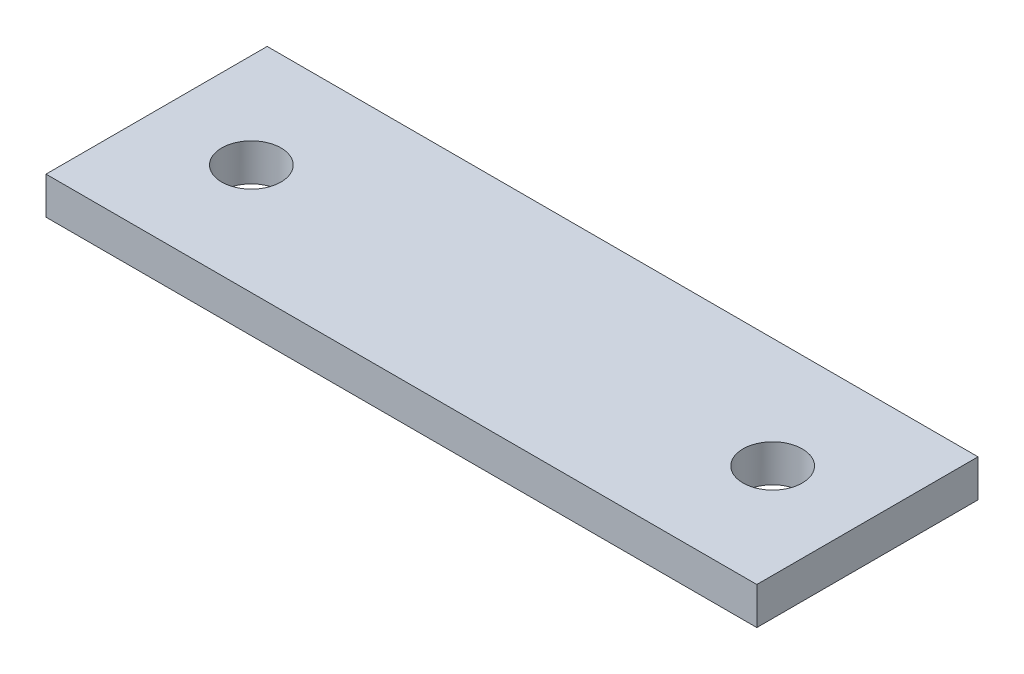
SolidWorks part; units mm, degrees
ref_plane "Front Plane" through (0, 0, 0) normal (0, 0, 1) x (1, 0, 0)
ref_plane "Top Plane" through (0, 0, 0) normal (0, 1, 0) x (1, 0, 0)
ref_plane "Right Plane" through (0, 0, 0) normal (1, 0, 0) x (0, 0, -1)
sketch "Sketch1" plane through (0, 0, 0) normal (0, 1, 0) x (1, 0, 0)
  line L1 (0, 0) -> (60, 0)
  line L2 (0, 0) -> (0, 18.67)
  line L3 (0, 18.67) -> (60, 18.67)
  line L4 (60, 0) -> (60, 18.67)
  dimension "D1" = 60
  dimension "D2" = 18.67
extrude "Boss-Extrude1" add sketch "Sketch1" along normal blind 3.15
sketch "Sketch2" plane through (0, 0, 0) normal (0, -1, 0) x (-1, 0, 0)
  line L0 (-60, 9.335) -> (0, 9.335)
  line L1 (-60, 0) -> (-60, 18.67) construction
  line L2 (0, 18.67) -> (0, 0) construction
  line L3 (0, 9.335) -> (-30, 9.335)
  line L4 (-30, 9.335) -> (-30, 18.67)
  line L5 (-60, 18.67) -> (0, 18.67) construction
hole_wizard "Ø5.0mm Dowel Hole1" positions "Sketch3" profile "Sketch4" hole size "Ø5.0" standard "ANSI Metric" end condition up to next
sketch "Sketch3" plane through (0, 3.15, 0) normal (0, 1, 0) x (1, 0, 0)
  point P0 (8, 9.335)
  point P3 (52, 9.335)
  point P7 (0, 0)
  point P8 (0, 0)
sketch "Sketch4" plane through (8, 3.15, -9.335) normal (1, 0, 0) x (0, 0, 1)
  line L0 (0, 0) -> (0, 3.15)
  line L1 (0, 3.15) -> (2.5, 3.15)
  line L2 (2.5, 3.15) -> (2.5, 0)
  line L5 (2.5, 0) -> (0, 0)
  line L11 (0, -6.35) -> (0, 107.95) construction
  dimension "Thru Hole Dia." = 5
  dimension "Thru Hole Depth" = 3.15
